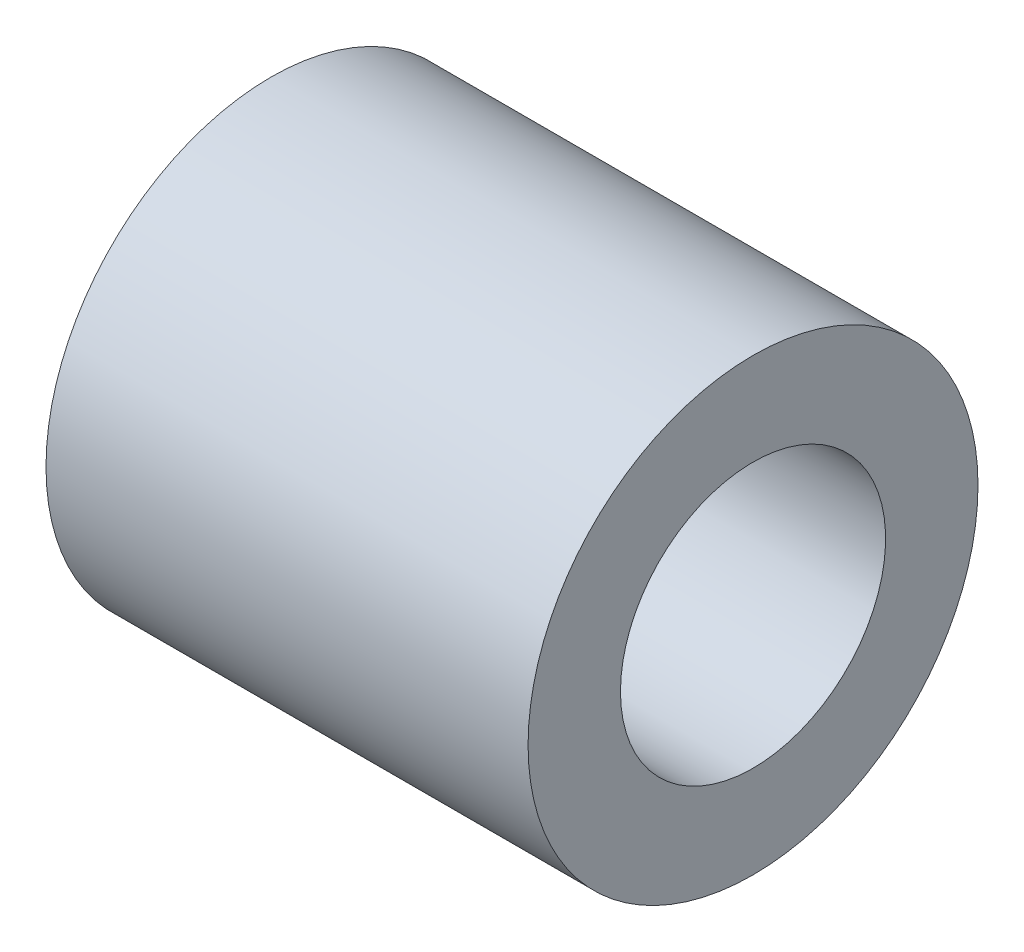
SolidWorks part; units mm, degrees
ref_plane "Front Plane" through (0, 0, 0) normal (0, 0, 1) x (1, 0, 0)
ref_plane "Top Plane" through (0, 0, 0) normal (0, 1, 0) x (1, 0, 0)
ref_plane "Right Plane" through (0, 0, 0) normal (1, 0, 0) x (0, 0, -1)
sketch "Insert_M4 Sketch" plane through (0, 0, 0) normal (0, 0, 1) x (1, 0, 0)
  line L0 (-400, 0) -> (400, 0) construction
  line L1 (0, 1.65) -> (6, 1.65)
  line L2 (6, 1.65) -> (6, 2.8)
  line L3 (6, 2.8) -> (0, 2.8)
  line L4 (0, 2.8) -> (0, 1.65)
revolve "Insert_M4" add sketch "Insert_M4 Sketch" angle 360 about L0
ref_axis "Engine Axis" through (6.3, 0, 0) along (-1, 0, 0)
